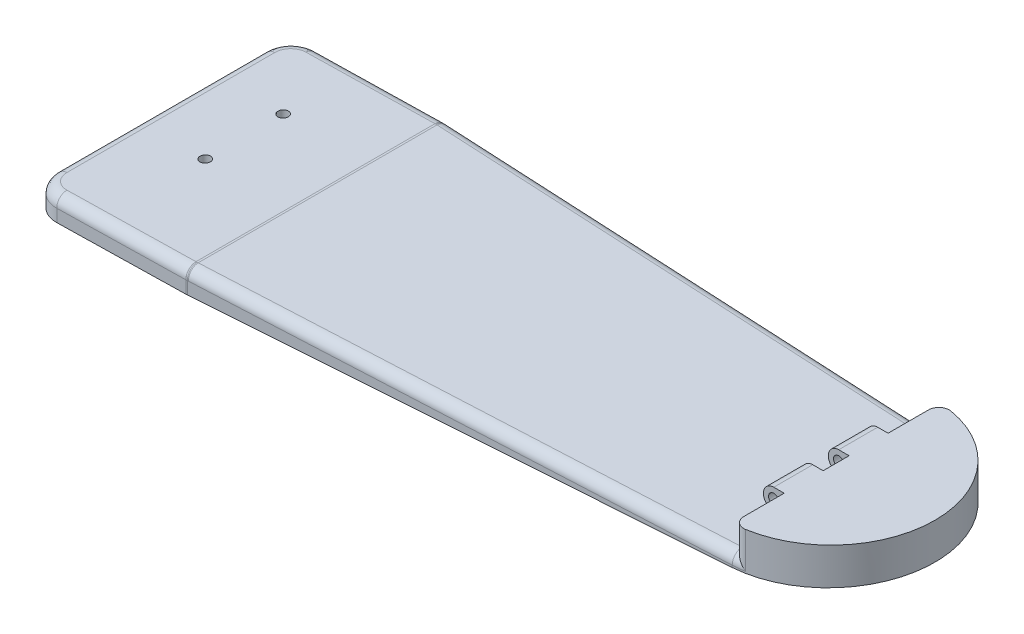
SolidWorks part; units mm, degrees
ref_plane "Front Plane" through (0, 0, 0) normal (0, 0, 1) x (1, 0, 0)
ref_plane "Top Plane" through (0, 0, 0) normal (0, 1, 0) x (1, 0, 0)
ref_plane "Right Plane" through (0, 0, 0) normal (1, 0, 0) x (0, 0, -1)
other "Configuration Table"
sketch "Sketch1" plane through (0, 0, 0) normal (0, 1, 0) x (1, 0, 0)
  line L0 (0, -25.4) -> (0, 25.4)
  line L1 (0, -25.4) -> (-127, -31.75)
  line L2 (-127, -31.75) -> (-165.1, -31.75)
  line L3 (-127, 31.75) -> (0, 25.4)
  line L4 (-165.1, 0) -> (0, 0) construction
  line L5 (-165.1, -31.75) -> (-165.1, 31.75)
  line L6 (-165.1, 31.75) -> (-127, 31.75)
  arc A0 (0, -25.4) -> (0, 25.4) centre (-1.27, 0) ccw
  point P4 (0, 0)
  dimension "D1" = 50.8
  dimension "D2" = 165.1
  dimension "D3" = 38.1
  dimension "D4" = 63.5
extrude "Boss-Extrude1" add sketch "Sketch1" against normal blind 6.35 contours L0 A0 | L4 L1 L0 | L4 L0 L3 region at (-85.9014, 0, 0) region at (10.213, 0, 0)
sketch "Sketch2" plane through (0, 0, 0) normal (0, 1, 0) x (1, 0, 0)
  line L4 (0, -25.4) -> (0, 25.4)
  arc A0 (0, -25.4) -> (0, 25.4) centre (-1.27, 0) ccw construction
  arc A1 (0, -25.4) -> (0, 25.4) centre (-1.27, 0) ccw
extrude "Boss-Extrude2" add sketch "Sketch2" along normal blind 6.35
sketch "Sketch3" plane through (0, 0, 0) normal (0, 0, 1) x (1, 0, 0)
  line L0 (2.54, 3.81) -> (-2.54, 3.81) construction
  line L1 (0, 6.35) -> (0, 0) construction
  line L2 (2.54, 1.27) -> (-2.54, 1.27)
  line L3 (2.54, 6.35) -> (-2.54, 6.35)
  line L4 (24.1617, 6.35) -> (0, 6.35) construction
  line L5 (0, 6.35) -> (0, 1.27)
  arc A0 (2.54, 1.27) -> (2.54, 6.35) centre (2.54, 3.81) ccw
  arc A1 (-2.54, 6.35) -> (-2.54, 1.27) centre (-2.54, 3.81) ccw
  circle A2 centre (-2.54, 3.81) radius 1.27
  point P4 (0, 3.81)
  dimension "D1" = 2.54
  dimension "D2" = 2.54
  dimension "D3" = 2.54
extrude "Boss-Extrude3" add sketch "Sketch3" along normal mid plane 25.4 contours L3 A1 L2 L5 A2 region at (-1.27, 1.3418, 0)
extrude "Cut-Extrude2" cut sketch "Sketch3<2>" against normal mid plane 6.35 contours L3 A1 L2 L5 A2 region at (-1.27, 1.3418, 0)
sketch "Sketch3<2>" plane through (0, 0, 0) normal (0, 0, 1) x (1, 0, 0) same geometry as "Sketch3"
sketch "Sketch4" plane through (0, 0, 0) normal (0, 0, 1) x (1, 0, 0)
  line L0 (-165.1, -6.35) -> (24.1617, -2.54)
  line L1 (24.1617, -6.35) -> (24.1617, 6.35) construction
  line L2 (24.1617, -2.54) -> (24.1617, -6.35)
  line L3 (24.1617, -6.35) -> (-165.1, -6.35)
  line L4 (-165.1, -0.767) -> (-127, 0)
  line L6 (0, 0) -> (-127, 0) construction
  line L7 (-127, 0) -> (-165.1, 0)
  line L8 (-165.1, 0) -> (-165.1, -0.767)
  line L9 (-165.1, -6.35) -> (-165.1, 0) construction
  dimension "D1" = 3.81
extrude "Cut-Extrude1" cut sketch "Sketch4" against normal through all both and the other way through all
fillet "Fillet1" radius 25.4 1 edges at (-127, 0, 0)
fillet "Fillet2" radius 6.35 4 edges at (-127, -2.7922, 31.75) (-127, -2.7922, -31.75) (-165.1, -3.5585, -31.75) (-165.1, -3.5585, 31.75)
fillet "Fillet3" radius 2.54 15 edges at (0, 3.175, -25.4) (0, 3.175, 25.4) (-63.3722, 0, -28.5686) (-126.793, 0, -31.7396) (-127.2071, -0.0042, -31.75) (-143.0028, -0.3221, -31.75) (-163.2401, -0.7295, -29.8901) (-165.1, -0.767, 0) (-163.2401, -0.7295, 29.8901) (-143.0028, -0.3221, 31.75) (-127.2071, -0.0042, 31.75) (-126.793, 0, 31.7396) (-63.3722, 0, 28.5686)
scale "Scale1" scale about centroid uniform scaling yes scale factor 1.5
hole_wizard "CBORE for #6 Pan Head Machine Screw1" positions "Sketch6" profile "Sketch5" counterbore size "#6" standard "ANSI Inch" end condition through all
sketch "Sketch6" plane through (0.0888, -4.4089, 0) normal (0.0201, -0.9998, 0) x (-0.9998, -0.0201, 0)
  line L0 (209.5137, -38.1) -> (209.5137, 38.1) construction
  line L1 (152.5902, 47.625) -> (199.9868, 47.625) construction
  point P0 (184.1137, 19.685)
  point P2 (184.1137, -8.89)
  dimension "D1" = 28.575
  dimension "D2" = 25.4
  dimension "D3" = 27.94
sketch "Sketch5" plane through (-183.9877, -8.1145, -19.685) normal (0, 0, 1) x (0.9998, 0.0201, 0)
  line L0 (0, 0) -> (0, 19.0461)
  line L1 (0, 19.0461) -> (1.8986, 19.0461)
  line L3 (1.8986, 19.0461) -> (1.8987, 2.54)
  line L4 (1.8987, 2.54) -> (3.7706, 2.54)
  line L5 (3.7706, 2.54) -> (3.7706, 0)
  line L7 (3.7706, 0) -> (0, 0)
  line L11 (0, -6.35) -> (0, 107.95) construction
  dimension "Thru Hole Dia." = 3.7973
  dimension "Thru Hole Depth" = 19.0461
  dimension "C'Bore Dia." = 7.5413
  dimension "C'Bore Depth" = 2.54
